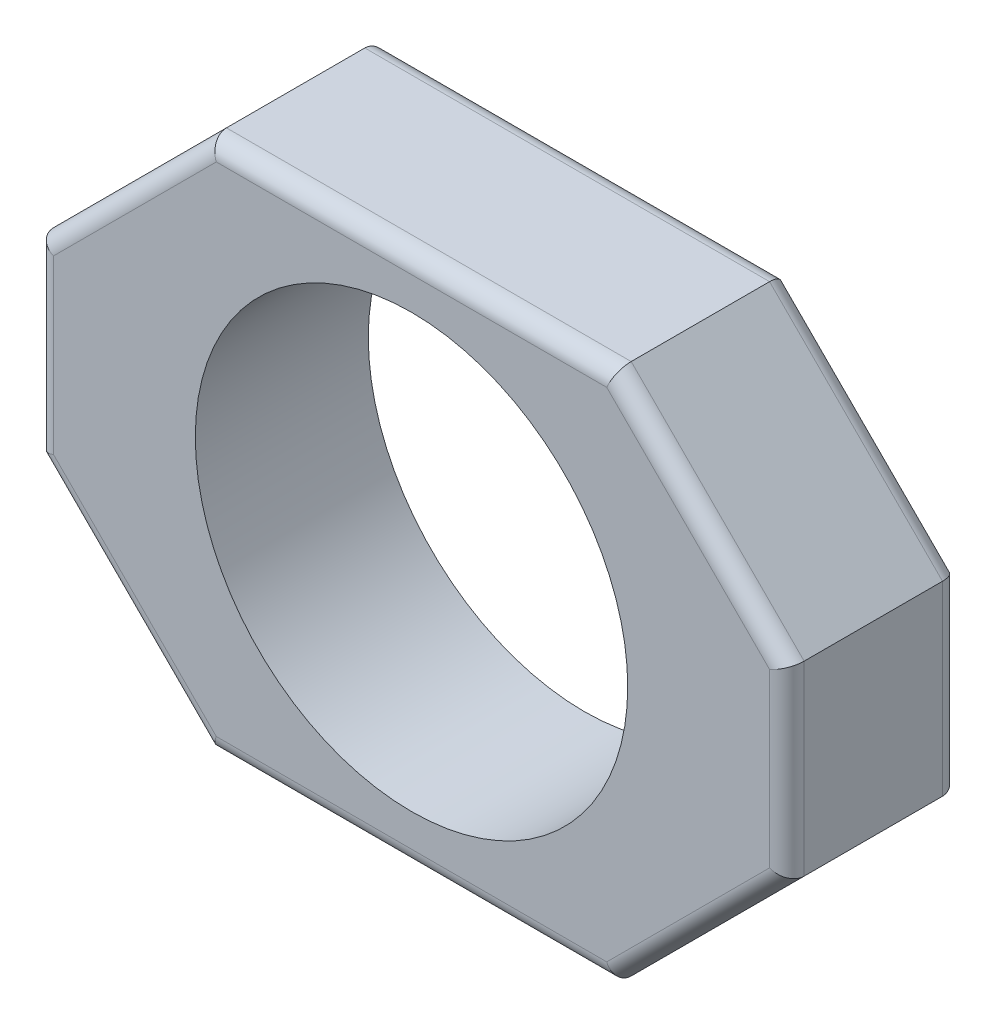
SolidWorks part; units mm, degrees
ref_plane "Front Plane" through (0, 0, 0) normal (0, 0, 1) x (1, 0, 0)
ref_plane "Top Plane" through (0, 0, 0) normal (0, 1, 0) x (1, 0, 0)
ref_plane "Right Plane" through (0, 0, 0) normal (1, 0, 0) x (0, 0, -1)
sketch "Sketch1" plane through (0, 0, 0) normal (0, 0, 1) x (1, 0, 0)
  line L1 (-55.1185, -39.0725) -> (55.1185, -39.0725)
  line L2 (-55.1185, -39.0725) -> (-55.1185, 39.0725)
  line L3 (-55.1185, 39.0725) -> (55.1185, 39.0725)
  line L4 (55.1185, -39.0725) -> (55.1185, 39.0725)
  line L5 (-55.1185, -39.0725) -> (55.1185, 39.0725) construction
  line L6 (-55.1185, 39.0725) -> (55.1185, -39.0725) construction
  point P0 (0, 0)
extrude "Boss-Extrude1" add sketch "Sketch1" against normal blind 25.4
sketch "Sketch2" plane through (0, 0, 0) normal (0, 0, 1) x (1, 0, 0)
  circle A0 centre (0, 0) radius 31.75
  dimension "D1" = 63.5
extrude "Cut-Extrude1" cut sketch "Sketch2" against normal through all
chamfer "Chamfer1" distance 25.4 angle 45 4 edges at (-55.1185, -39.0725, -12.7) (55.1185, -39.0725, -12.7) (-55.1185, 39.0725, -12.7) (55.1185, 39.0725, -12.7)
fillet "Fillet1" radius 2.54 16 edges at (-42.4185, 26.3725, -25.4) (-55.1185, 0, -25.4) (-42.4185, -26.3725, -25.4) (0, -39.0725, -25.4) (42.4185, -26.3725, -25.4) (55.1185, 0, -25.4) (0, 39.0725, -25.4) (42.4185, 26.3725, -25.4) (-42.4185, 26.3725, 0) (-55.1185, 0, 0) (-42.4185, -26.3725, 0) (0, -39.0725, 0) (42.4185, -26.3725, 0) (55.1185, 0, 0) (42.4185, 26.3725, 0) (0, 39.0725, 0)
